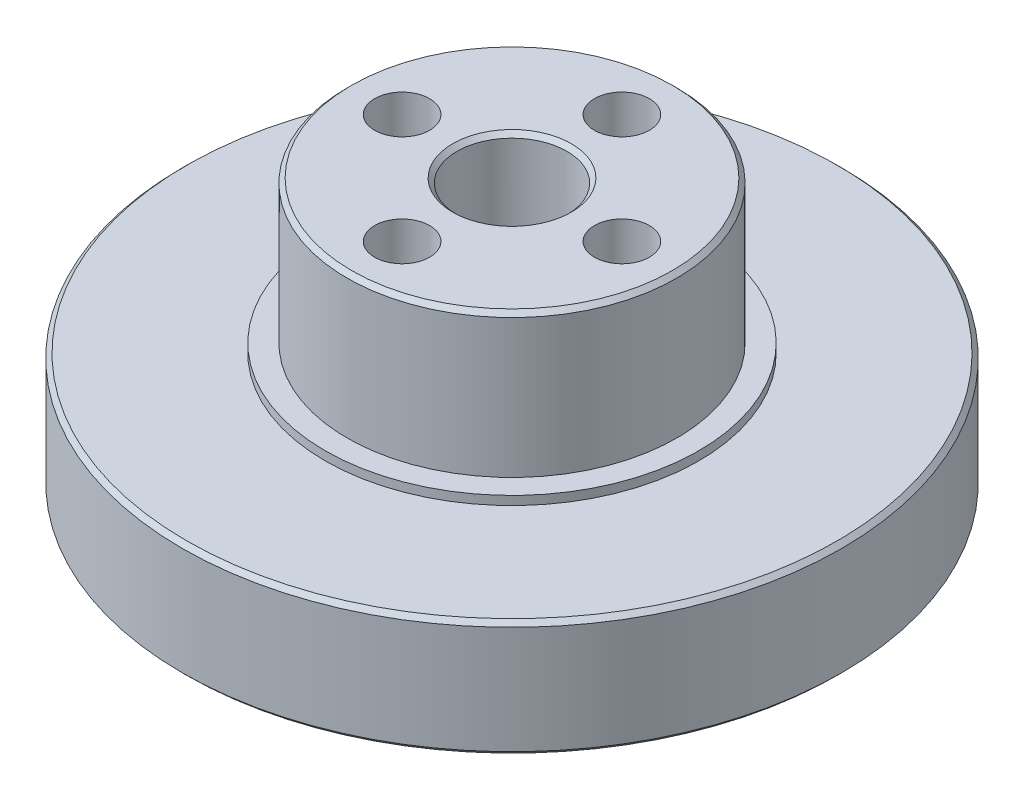
SolidWorks part; units mm, degrees
ref_plane "前视基准面" through (0, 0, 0) normal (0, 0, 1) x (1, 0, 0)
ref_plane "上视基准面" through (0, 0, 0) normal (0, 1, 0) x (1, 0, 0)
ref_plane "右视基准面" through (0, 0, 0) normal (1, 0, 0) x (0, 0, -1)
other "Configuration Table"
sketch "草图1" plane through (0, 0, 0) normal (0, 1, 0) x (1, 0, 0)
  circle A0 centre (0, 0) radius 11.525 construction
  circle A1 centre (0, 11.525) radius 1.83
  circle A2 centre (9.9809, 5.7625) radius 1.83
  circle A3 centre (9.9809, -5.7625) radius 1.83
  circle A4 centre (0, -11.525) radius 1.83
  circle A5 centre (-9.9809, -5.7625) radius 1.83
  circle A6 centre (-9.9809, 5.7625) radius 1.83
  circle A8 centre (0, 0) radius 15
  point P18 (0, 0)
  dimension "D1" = 23.05
  dimension "D2" = 3.66
  dimension "D5" = 30
  dimension "D3" = 6
extrude "凸台-拉伸1" add sketch "草图1" along normal blind 3.7
sketch "草图2" plane through (0, 3.7, 0) normal (0, 1, 0) x (1, 0, 0)
  circle A0 centre (0, 0) radius 15
extrude "凸台-拉伸2" add sketch "草图2" along normal blind 1.6
sketch "草图3" plane through (0, 5.3, 0) normal (0, 1, 0) x (1, 0, 0)
  circle A0 centre (0, 0) radius 8.5
  dimension "D1" = 17
extrude "凸台-拉伸3" add sketch "草图3" along normal blind 0.4
sketch "草图4" plane through (0, 5.7, 0) normal (0, 1, 0) x (1, 0, 0)
  circle A0 centre (0, 0) radius 7.5
  dimension "D1" = 15
extrude "凸台-拉伸4" add sketch "草图4" along normal blind 6.5
sketch "草图5" plane through (0, 12.2, 0) normal (0, 1, 0) x (1, 0, 0)
  circle A0 centre (0, 5) radius 1.25
  circle A1 centre (5, 0) radius 1.25
  circle A2 centre (0, -5) radius 1.25
  circle A3 centre (-5, 0) radius 1.25
  circle A4 centre (0, 0) radius 2.5
  point P12 (0, 0)
  dimension "D1" = 2.5
  dimension "D2" = 5
  dimension "D4" = 5
  dimension "D3" = 4
extrude "切除-拉伸1" cut sketch "草图5" against normal blind 7
chamfer "倒角1" distance 0.2 angle 45 10 edges at (-9.9809, 0, -3.9325) (-9.9809, 0, 7.5925) (0, 0, 13.355) (9.9809, 0, 7.5925) (9.9809, 0, -3.9325) (0, 0, -9.695) (0, 0, 15) (0, 12.2, 7.5) (0, 5.3, 15) (0, 12.2, 2.5)
sketch "草图7" plane through (0, 5.2, 0) normal (0, 1, 0) x (1, 0, 0)
  circle A2 centre (0, 0) radius 2.5 construction
  circle A3 centre (0, 0) radius 2.5
extrude "切除-拉伸4" cut sketch "草图7" against normal through all
sketch "草图8" plane through (0, 0, 0) normal (0, -1, 0) x (-1, 0, 0)
  circle A0 centre (0, 0) radius 6
  dimension "D1" = 6
extrude "切除-拉伸5" cut sketch "草图8" against normal blind 2
chamfer "倒角2" distance 0.5 angle 45 3 edges at (0, 0, -6) (0, 2, -2.5) (0, 2, -6)
